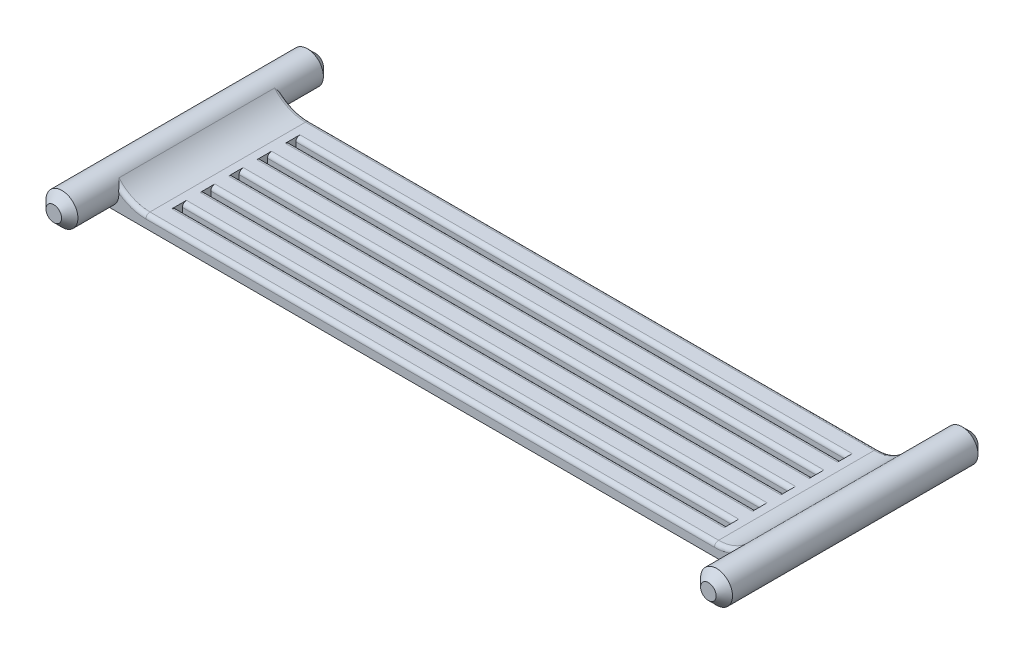
SolidWorks part; units mm, degrees
ref_plane "Front Plane" through (0, 0, 0) normal (0, 0, 1) x (1, 0, 0)
ref_plane "Top Plane" through (0, 0, 0) normal (0, 1, 0) x (1, 0, 0)
ref_plane "Right Plane" through (0, 0, 0) normal (1, 0, 0) x (0, 0, -1)
sketch "Sketch1" plane through (0, 0, 0) normal (0, 1, 0) x (1, 0, 0)
  line L1 (40, -10) -> (-40, -10)
  line L2 (40, -10) -> (40, 10)
  line L3 (40, 10) -> (-40, 10)
  line L4 (-40, -10) -> (-40, 10)
  line L5 (0, 10) -> (0, -10) construction
  line L6 (40, 0) -> (-40, 0) construction
  point P0 (0, 0)
  dimension "D1" = 20
  dimension "D2" = 80
extrude "Boss-Extrude1" add sketch "Sketch1" along normal blind 1.5
sketch "Sketch2" plane through (0, 0, 10) normal (0, 0, 1) x (1, 0, 0)
  line L1 (-40, 1.5) -> (-40, 0) construction
  line L2 (40, 1.5) -> (40, 0) construction
  circle A0 centre (40, 1.95) radius 1.95
  circle A1 centre (-40, 1.95) radius 1.95
  dimension "D1" = 3.9
extrude "Boss-Extrude2" add sketch "Sketch2" against normal offset from surface 6 and the other way blind 6 contours A1 | A0 up to face at (0, 0.75, -10) offset beyond the face yes
fillet "Fillet1" radius 5 2 edges at (38.1026, 1.5, 0) (-38.1026, 1.5, 0)
sketch "Sketch4" [suppressed] plane through (0, 0, 0) normal (1, 0, 0) x (0, 0, -1)
  line L0 (4.6015, 26.0967) -> (1.6471, 26.6176)
  line L1 (4.6015, -26.0967) -> (1.6471, -26.6176)
  line L2 (0, 0) -> (4.6015, 26.0967) construction
  line L3 (0, 0) -> (4.6015, -26.0967) construction
  arc A0 (4.6015, 26.0967) -> (4.6015, -26.0967) centre (0, 0) cw
  dimension "D2" = 26.4992
  dimension "D1" = 3
  dimension "D3" = 160
ref_plane "Plane1" [suppressed] through (0, 0, 0) normal (0, 0.1736, 0.9848) x (1, 0, 0)
sketch "Sketch7" [suppressed] plane through (0, 0, 0) normal (0, 0.1736, 0.9848) x (1, 0, 0)
  line L0 (0, 0) -> (0, 26.4992) construction
  line L1 (5, 25.7492) -> (-5, 25.7492)
  line L2 (5, 25.7492) -> (5, 27.2492)
  line L3 (5, 27.2492) -> (-5, 27.2492)
  line L4 (-5, 25.7492) -> (-5, 27.2492)
  line L5 (0, 27.2492) -> (0, 25.7492) construction
  line L6 (5, 26.4992) -> (-5, 26.4992) construction
  point P0 (0, 26.4992)
  dimension "D1" = 20
  dimension "D2" = 1.5
sweep "Sweep2" [suppressed] add profiles "Sketch7" path "Sketch4"
sketch "Sketch6" [suppressed] plane through (5, 0, 0) normal (-1, 0, 0) x (0, 0, 1)
  line L2 (-1.7774, -27.3562) -> (-1.5169, -25.879) construction
  line L3 (-1.7774, 27.3562) -> (-1.5169, 25.879) construction
  circle A0 centre (-1.8555, 27.7994) radius 1.95
  circle A1 centre (-1.8555, -27.7994) radius 1.95
  dimension "D1" = 3.9
  dimension "D2" = 3.9
extrude "Boss-Extrude3" [suppressed] add sketch "Sketch6" along normal blind 5 and the other way offset from surface 5
fillet "Fillet2" [suppressed] radius 5
sketch "Sketch8" plane through (0, 1.5, 0) normal (0, 1, 0) x (1, 0, 0)
  line L0 (34.7464, -10) -> (34.7464, 10) construction
  line L1 (33.7464, -0.4) -> (-33.7464, -0.4)
  line L2 (33.7464, -0.4) -> (33.7464, 0.4)
  line L3 (33.7464, 0.4) -> (-33.7464, 0.4)
  line L5 (33.7464, 7.3333) -> (33.7464, 10) construction
  line L6 (33.7464, 0) -> (-33.7464, 0) construction
  line L11 (33.7464, 3.0667) -> (-33.7464, 3.0667)
  line L12 (33.7464, 3.0667) -> (33.7464, 3.8667)
  line L17 (33.7464, 3.8667) -> (-33.7464, 3.8667)
  line L19 (33.7464, -6.9333) -> (-33.7464, -6.9333) construction
  line L20 (33.7464, 3.4667) -> (-33.7464, 3.4667) construction
  line L21 (33.7464, 6.5333) -> (-33.7464, 6.5333)
  line L22 (33.7464, 6.5333) -> (33.7464, 7.3333)
  line L23 (33.7464, 7.3333) -> (-33.7464, 7.3333)
  line L25 (33.7464, -3.4667) -> (-33.7464, -3.4667) construction
  line L26 (33.7464, 6.9333) -> (-33.7464, 6.9333) construction
  line L32 (34.7464, 10) -> (-34.7464, 10) construction
  line L33 (-33.7464, -7.3333) -> (-33.7464, -6.5333)
  line L34 (-33.7464, -3.8667) -> (-33.7464, -3.0667)
  line L37 (-33.7464, 3.8667) -> (-33.7464, 3.0667)
  line L38 (-33.7464, 7.3333) -> (-33.7464, 6.5333)
  line L40 (-33.7464, 0.4) -> (-33.7464, -0.4)
  line L43 (33.7464, 0.4) -> (33.7464, 3.0667) construction
  line L48 (33.7464, -7.3333) -> (-33.7464, -7.3333)
  line L49 (33.7464, -6.5333) -> (33.7464, -7.3333)
  line L50 (33.7464, -6.5333) -> (-33.7464, -6.5333)
  line L51 (33.7464, -3.8667) -> (-33.7464, -3.8667)
  line L52 (33.7464, -3.0667) -> (33.7464, -3.8667)
  line L53 (33.7464, -3.0667) -> (-33.7464, -3.0667)
  line L54 (33.7464, 10) -> (33.7464, 10.8) [skipped]
  line L55 (33.7464, 10.8) -> (-33.7464, 10.8) [skipped]
  line L56 (33.7464, 10.4) -> (-33.7464, 10.4) construction
  line L57 (33.7464, 10) -> (-33.7464, 10) [skipped]
  point P0 (0, 0)
  point P10 (0, 10.4)
  point P16 (0, 6.9333)
  point P18 (0, 3.4667)
  dimension "D1" = 0.8
  dimension "D2" = 1
  dimension "D3" = 4
extrude "Cut-Extrude1" cut sketch "Sketch8" against normal through all
fillet "Fillet3" radius 0.5 16 edges at (-36.8241, 1.9521, 10) (36.8241, 1.9521, 10) (36.8241, 1.9521, -10) (-36.8241, 1.9521, -10) (0, 1.5, 10) (0, 1.5, -10) (0, 1.5, 7.3333) (0, 1.5, 6.5333) (0, 1.5, 3.8667) (0, 1.5, 3.0667) (0, 1.5, 0.4) (0, 1.5, -0.4) (0, 1.5, -3.0667) (0, 1.5, -3.8667) (0, 1.5, -6.5333) (0, 1.5, -7.3333)
chamfer "Chamfer1" distance 1 angle 45 4 edges at (-38.05, 1.95, -16) (-38.05, 1.95, 16) (41.95, 1.95, 16) (41.95, 1.95, -16)
equation "\"D2@Sketch4\"=(\"D2@Sketch1\"-2*\"D1@Sketch4\")*(360/\"D3@Sketch4\")/6.2832"
equation "\"bandwidth\"= 20mm"
equation "\"D1@Sketch1\"=\"bandwidth\""
equation "\"D1@Sketch7\"=\"bandwidth\""
equation "\"loosefit\"= 0.5mm"
equation "\"tightfit\"= 0.2mm"
